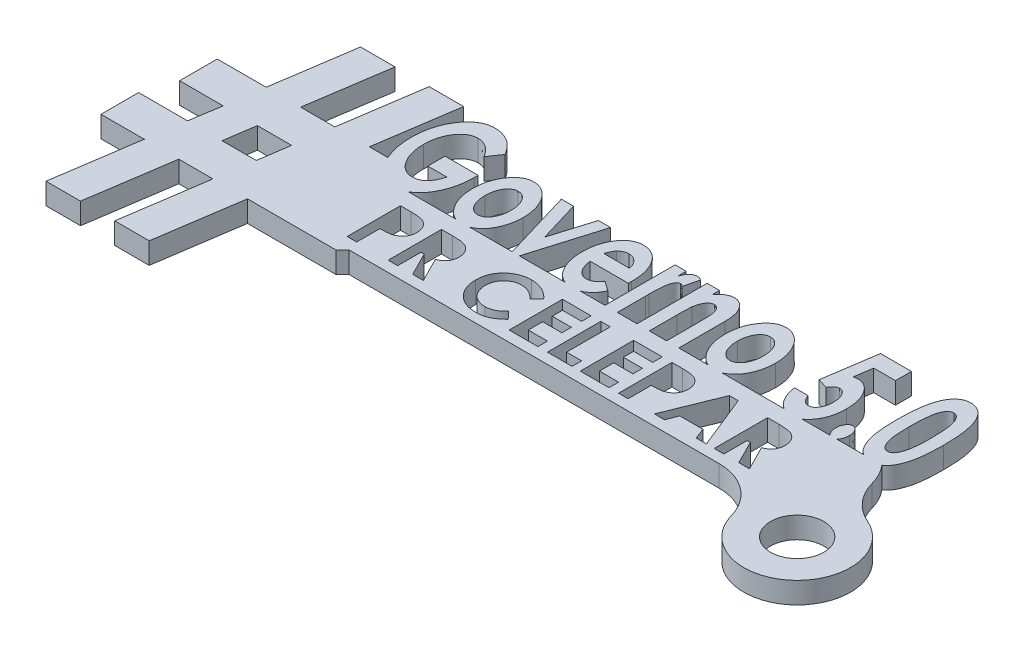
SolidWorks part; units mm, degrees
ref_plane "Front Plane" through (0, 0, 0) normal (0, 0, 1) x (1, 0, 0)
ref_plane "Top Plane" through (0, 0, 0) normal (0, 1, 0) x (1, 0, 0)
ref_plane "Right Plane" through (0, 0, 0) normal (1, 0, 0) x (0, 0, -1)
sketch "Sketch1" plane through (0, 0, 0) normal (0, 1, 0) x (1, 0, 0)
  line L1 (0, 0) -> (100, 0)
  line L2 (0, 0) -> (0, 15)
  line L3 (0, 15) -> (100, 15)
  line L4 (100, 0) -> (100, 15)
  dimension "D1" = 100
  dimension "D2" = 15
extrude "Boss-Extrude1" add sketch "Sketch1" along normal blind 4
sketch "Sketch2" plane through (0, 4, 0) normal (0, 1, 0) x (1, 0, 0)
  text T0 "<b>Governo 5.0</b>" font "Century Gothic" height 18
extrude "Boss-Extrude2" add sketch "Sketch2" against normal blind 4
sketch "Sketch3" plane through (0, 4, 0) normal (0, 1, 0) x (1, 0, 0)
  line L0 (0, 2) -> (100, 2) construction
  line L1 (0, 15) -> (0, 0) construction
  line L2 (100, 0) -> (100, 15) construction
  line L3 (0, 0) -> (100, 0) construction
  text T0 "<b>PR CELEPAR</b>" font "Century Gothic" height 10
  dimension "D1" = 2
extrude "Cut-Extrude1" cut sketch "Sketch3" against normal blind 4
sketch "Sketch4" plane through (0, 4, 0) normal (0, 1, 0) x (1, 0, 0)
  text T0 "<b>#</b>" font "Century Gothic" height 50
extrude "Boss-Extrude7" add sketch "Sketch4" against normal blind 4
sketch "Sketch5" plane through (0, 4, 0) normal (0, 1, 0) x (1, 0, 0)
  line L1 (100, 0) -> (100, 15) construction
  circle A0 centre (102, -4.5826) radius 10
  circle A1 centre (102, -4.5826) radius 5
  dimension "D1" = 10
  dimension "D2" = 5
  dimension "D4" = 2
  dimension "D3" = 5
sketch "Sketch8" plane through (0, 4, 0) normal (0, 1, 0) x (1, 0, 0)
  line L1 (-6.5382, 4.3193) -> (4.308, 4.3193)
  line L2 (-6.5382, 4.3193) -> (-6.5382, 14.8102)
  line L3 (-6.5382, 14.8102) -> (4.308, 14.8102)
  line L4 (4.308, 4.3193) -> (4.308, 14.8102)
chamfer "Chamfer1" distance 10 angle 45 1 edges at (3.3602, 2, 0)
sketch "Sketch9" plane through (0, 4, 0) normal (0, 1, 0) x (1, 0, 0)
  line L0 (72.0272, 5.8462) -> (75.024, 5.8462)
  line L1 (81.6667, 8.1538) -> (84.519, 8.1538)
  line L2 (81.6667, 8.1538) -> (81.6667, 10.2051)
  line L3 (81.6667, 10.2051) -> (84.519, 10.2051)
  line L4 (84.519, 8.1538) -> (84.519, 10.2051)
  line L5 (75.024, 5.8462) -> (73.5256, 9.3177)
  line L6 (73.5256, 9.3177) -> (72.0272, 5.8462)
  line L7 (20.5128, 10.2051) -> (20.5128, 8.1538) construction
  line L8 (63.7179, 8.1538) -> (66.6989, 8.1538)
  line L9 (63.7179, 8.1538) -> (63.7179, 10.2051)
  line L10 (63.7179, 10.2051) -> (66.6989, 10.2051)
  line L11 (66.6989, 8.1538) -> (66.6989, 10.2051)
  line L12 (20.5128, 8.1538) -> (23.6452, 8.1538)
  line L13 (20.5128, 8.1538) -> (20.5128, 10.2051)
  line L14 (20.5128, 10.2051) -> (23.6452, 10.2051)
  line L15 (23.6452, 8.1538) -> (23.6452, 10.2051)
  line L17 (12.8205, 8.1538) -> (16.1734, 8.1538)
  line L18 (12.8205, 8.1538) -> (12.8205, 10.2051)
  line L19 (12.8205, 10.2051) -> (16.1734, 10.2051)
  line L20 (16.1734, 8.1538) -> (16.1734, 10.2051)
extrude "Cut-Extrude2" cut sketch "Sketch9" against normal blind 4
extrude "Boss-Extrude12" add sketch "Sketch8" against normal blind 4
extrude "Boss-Extrude13" add sketch "Sketch5" against normal blind 4 contours A0
sketch "Sketch11" plane through (0, 4, 0) normal (0, 1, 0) x (1, 0, 0)
  circle A0 centre (102, -4.5826) radius 5
  dimension "D1" = 10
extrude "Cut-Extrude3" cut sketch "Sketch11" against normal blind 4
fillet "Fillet3" radius 10 1 edges at (100, 2, -5.2154)
fillet "Fillet4" radius 10 1 edges at (100, 2, -15)
fillet "Fillet5" radius 10 1 edges at (93.1118, 2, 0)
